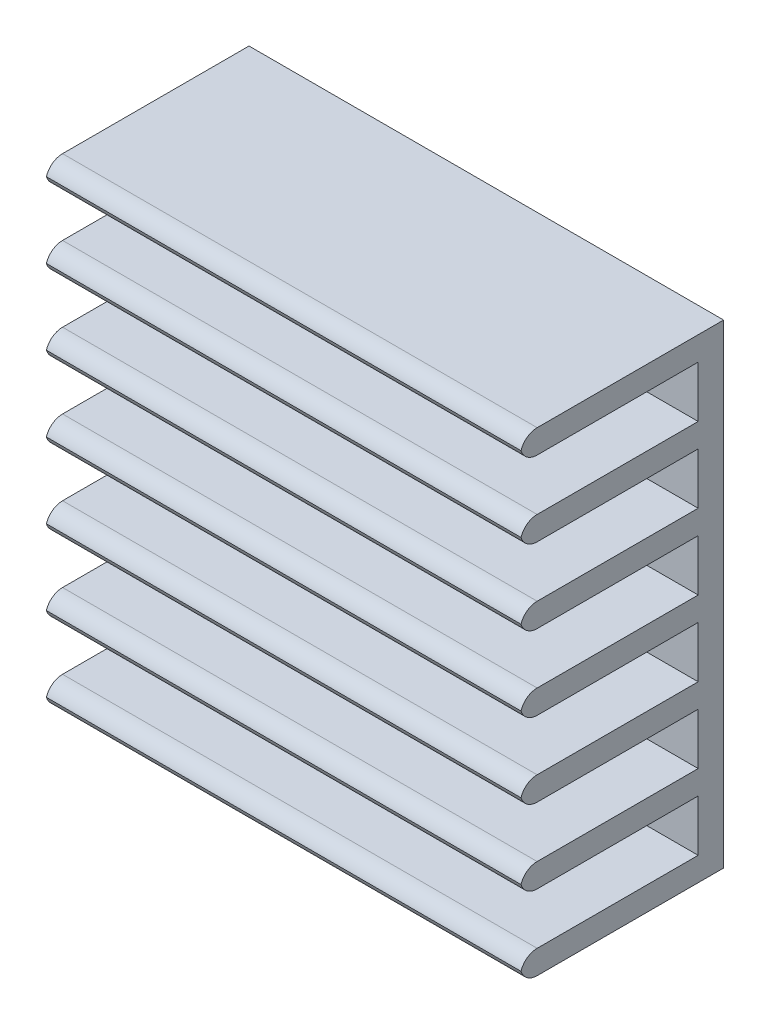
SolidWorks part; units mm, degrees
material "1060 Alloy"
ref_plane "Front Plane" through (0, 0, 0) normal (0, 0, 1) x (1, 0, 0)
ref_plane "Top Plane" through (0, 0, 0) normal (0, 1, 0) x (1, 0, 0)
ref_plane "Right Plane" through (0, 0, 0) normal (1, 0, 0) x (0, 0, -1)
sketch "Sketch1" plane through (0, 0, 0) normal (1, 0, 0) x (0, 0, -1)
  line L0 (0, 7) -> (0, -7) construction
  line L1 (-6, 4.7833) -> (-6, 4.0833)
  line L2 (-6, 7) -> (0, 7)
  line L3 (-6, 7) -> (-6, 6.3)
  line L4 (-6, 6.3) -> (-0.75, 6.3)
  line L5 (0, 7) -> (0, 6.3)
  line L6 (-6, 4.7833) -> (-0.75, 4.7833)
  line L7 (0, 4.7833) -> (0, 4.0833)
  line L8 (-6, 4.0833) -> (-0.75, 4.0833)
  line L9 (-6, 2.5667) -> (-6, 1.8667)
  line L10 (-6, 2.5667) -> (-0.75, 2.5667)
  line L11 (0, 2.5667) -> (0, 1.8667)
  line L12 (-6, 1.8667) -> (-0.75, 1.8667)
  line L13 (-6, 0.35) -> (-6, -0.35)
  line L14 (-6, 0.35) -> (-0.75, 0.35)
  line L15 (0, 0.35) -> (0, -0.35)
  line L16 (-6, -0.35) -> (-0.75, -0.35)
  line L17 (-6, -1.8667) -> (-6, -2.5667)
  line L18 (-6, -1.8667) -> (-0.75, -1.8667)
  line L19 (0, -1.8667) -> (0, -2.5667)
  line L20 (-6, -2.5667) -> (-0.75, -2.5667)
  line L21 (-6, -4.0833) -> (-6, -4.7833)
  line L22 (-6, -4.0833) -> (-0.75, -4.0833)
  line L23 (0, -4.0833) -> (0, -4.7833)
  line L24 (-6, -4.7833) -> (-0.75, -4.7833)
  line L25 (-6, -6.3) -> (-6, -7)
  line L26 (-6, -6.3) -> (-0.75, -6.3)
  line L27 (0, -6.3) -> (0, -7)
  line L28 (-6, -7) -> (0, -7)
  line L29 (-0.75, 6.3) -> (-0.75, 4.7833)
  line L30 (0, 6.3) -> (0, 4.7833)
  line L31 (0, 4.0833) -> (0, 2.5667)
  line L32 (0, 1.8667) -> (0, 0.35)
  line L33 (0, -0.35) -> (0, -1.8667)
  line L34 (0, -2.5667) -> (0, -4.0833)
  line L35 (0, -4.7833) -> (0, -6.3)
  line L36 (-0.75, 4.0833) -> (-0.75, 2.5667)
  line L37 (-0.75, 1.8667) -> (-0.75, 0.35)
  line L38 (-0.75, -0.35) -> (-0.75, -1.8667)
  line L39 (-0.75, -2.5667) -> (-0.75, -4.0833)
  line L40 (-0.75, -4.7833) -> (-0.75, -6.3)
  point P2 (0, 0)
  dimension "D1" = 0.7
  dimension "D2" = 6
  dimension "D4" = 14
  dimension "D5" = 1.5
  dimension "D3" = 7
extrude "Boss-Extrude1" add sketch "Sketch1" along normal mid plane 14
fillet "Fillet1" radius 0.5 14 edges at (0, -7, 6) (0, -6.3, 6) (0, -4.7833, 6) (0, -4.0833, 6) (0, -2.5667, 6) (0, -1.8667, 6) (0, -0.35, 6) (0, 0.35, 6) (0, 1.8667, 6) (0, 2.5667, 6) (0, 4.0833, 6) (0, 4.7833, 6) (0, 6.3, 6) (0, 7, 6)
